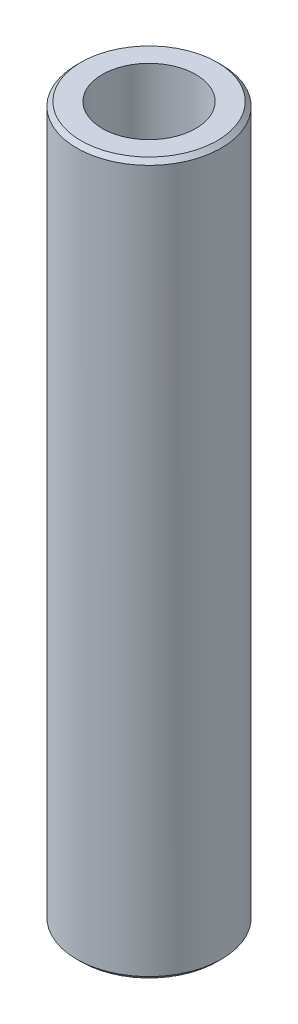
SolidWorks part; units mm, degrees
ref_plane "Front Plane" through (0, 0, 0) normal (0, 0, 1) x (1, 0, 0)
ref_plane "Top Plane" through (0, 0, 0) normal (0, 1, 0) x (1, 0, 0)
ref_plane "Right Plane" through (0, 0, 0) normal (1, 0, 0) x (0, 0, -1)
sketch "Sketch1" plane through (0, 0, 0) normal (0, 1, 0) x (1, 0, 0)
  circle A0 centre (0, 0) radius 40
  dimension "SHAFT_OD" = 80
extrude "Boss-Extrude1" add sketch "Sketch1" along normal blind 393.4926
sketch "Sketch2" plane through (0, 0, 0) normal (0, 1, 0) x (1, 0, 0)
  circle A0 centre (0, 0) radius 25.8936
  dimension "BORE_D" = 51.7872
extrude "Cut-Extrude1" cut sketch "Sketch2" along normal through all
chamfer "Chamfer1" distance 2.347 angle 45 2 edges at (0, 393.4926, 40) (0, 0, 40)
